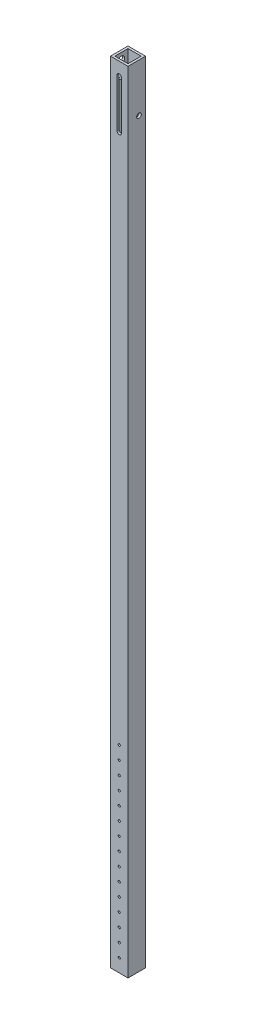
SolidWorks part; units mm, degrees
material "6061-T6 (SS)"
ref_plane "Front Plane" through (0, 0, 0) normal (0, 0, 1) x (1, 0, 0)
ref_plane "Top Plane" through (0, 0, 0) normal (0, 1, 0) x (1, 0, 0)
ref_plane "Right Plane" through (0, 0, 0) normal (1, 0, 0) x (0, 0, -1)
sketch "Sketch1" plane through (0, 0, 0) normal (0, 1, 0) x (1, 0, 0)
  line L0 (9.525, 9.525) -> (-9.525, 9.525)
  line L1 (12.7, -12.7) -> (-12.7, -12.7)
  line L2 (12.7, -12.7) -> (12.7, 12.7)
  line L3 (12.7, 12.7) -> (-12.7, 12.7)
  line L4 (-12.7, -12.7) -> (-12.7, 12.7)
  line L5 (12.7, -12.7) -> (-12.7, 12.7) construction
  line L6 (12.7, 12.7) -> (-12.7, -12.7) construction
  line L7 (-9.525, -9.525) -> (-9.525, 9.525)
  line L8 (9.525, -9.525) -> (-9.525, -9.525)
  line L9 (9.525, -9.525) -> (9.525, 9.525)
  point P0 (0, 0)
  dimension "D1" = 25.4
  dimension "D2" = 3.175
extrude "Boss-Extrude1" add sketch "Sketch1" along normal blind 1143
sketch "Sketch2" plane through (0, 0, -12.7) normal (0, 0, -1) x (-1, 0, 0)
  line L0 (0, 990.6) -> (0, 1104.9) construction
  line L1 (-3.175, 990.6) -> (-3.175, 1104.9)
  line L2 (3.175, 990.6) -> (3.175, 1104.9)
  line L3 (-12.7, 1143) -> (12.7, 1143) construction
  arc A0 (-3.175, 990.6) -> (3.175, 990.6) centre (0, 990.6) ccw
  arc A1 (3.175, 1104.9) -> (-3.175, 1104.9) centre (0, 1104.9) ccw
  point P3 (0, 1047.75)
  dimension "D2" = 38.1
  dimension "D1" = 6.35
  dimension "D3" = 114.3
extrude "Cut-Extrude1" cut sketch "Sketch2" against normal up to next
sketch "Sketch3" plane through (0, 0, 12.7) normal (0, 0, 1) x (1, 0, 0)
  line L0 (0, 1123.95) -> (0, 1054.1) construction
  line L1 (3.175, 1123.95) -> (3.175, 1054.1)
  line L2 (-3.175, 1123.95) -> (-3.175, 1054.1)
  line L3 (-12.7, 1143) -> (12.7, 1143) construction
  arc A0 (3.175, 1123.95) -> (-3.175, 1123.95) centre (0, 1123.95) ccw
  arc A1 (-3.175, 1054.1) -> (3.175, 1054.1) centre (0, 1054.1) ccw
  point P3 (0, 1089.025)
  dimension "D2" = 19.05
  dimension "D1" = 6.35
  dimension "D3" = 69.85
extrude "Cut-Extrude2" cut sketch "Sketch3" against normal up to next
sketch "Sketch4" plane through (-12.7, 0, 0) normal (-1, 0, 0) x (0, 0, 1)
  line L0 (-12.7, 1143) -> (12.7, 1143) construction
  line L2 (-12.7, 1143) -> (-12.7, 0) construction
  circle A0 centre (-3.175, 1073.15) radius 3.3782
  dimension "D1" = 6.7564
  dimension "D2" = 69.85
  dimension "D3" = 9.525
extrude "Cut-Extrude3" cut sketch "Sketch4" against normal through all
sketch "Sketch5" plane through (-12.7, 0, 0) normal (-1, 0, 0) x (0, 0, 1)
  line L0 (-12.7, 1143) -> (-12.7, 0) construction
  line L1 (-12.7, 1143) -> (12.7, 1143) construction
  line L2 (-12.7, 1143) -> (-12.7, 1104.9) construction
  circle A0 centre (0, 1133.475) radius 4.7625
  circle A1 centre (0, 1114.425) radius 4.7625
  dimension "D1" = 9.525
  dimension "D2" = 12.7
  dimension "D3" = 9.525
  dimension "D4" = 38.1
  dimension "D5" = 9.525
extrude "Cut-Extrude4" cut sketch "Sketch5" against normal up to next
sketch "Sketch6" plane through (0, 0, 12.7) normal (0, 0, 1) x (1, 0, 0)
  line L0 (-12.7, 0) -> (-12.7, 304.8) construction
  line L1 (-12.7, 1143) -> (-12.7, 0) construction
  line L2 (-12.7, 0) -> (12.7, 0) construction
  line L3 (12.7, 1143) -> (12.7, 0) construction
  circle A28 centre (0, 19.05) radius 1.5875
  circle A29 centre (0, 38.1) radius 1.5875
  circle A30 centre (0, 57.15) radius 1.5875
  circle A31 centre (0, 76.2) radius 1.5875
  circle A32 centre (0, 95.25) radius 1.5875
  circle A33 centre (0, 114.3) radius 1.5875
  circle A34 centre (0, 133.35) radius 1.5875
  circle A35 centre (0, 152.4) radius 1.5875
  circle A36 centre (0, 171.45) radius 1.5875
  circle A37 centre (0, 190.5) radius 1.5875
  circle A38 centre (0, 209.55) radius 1.5875
  circle A39 centre (0, 228.6) radius 1.5875
  circle A40 centre (0, 247.65) radius 1.5875
  circle A41 centre (0, 266.7) radius 1.5875
  circle A42 centre (0, 285.75) radius 1.5875
  dimension "D3" = 19.05
  dimension "D5" = 15
  dimension "D6" = 19.05
  dimension "D2" = 3.175
  dimension "D4" = 12.7
  dimension "D1" = 304.8
extrude "Cut-Extrude5" cut sketch "Sketch6" against normal through all
